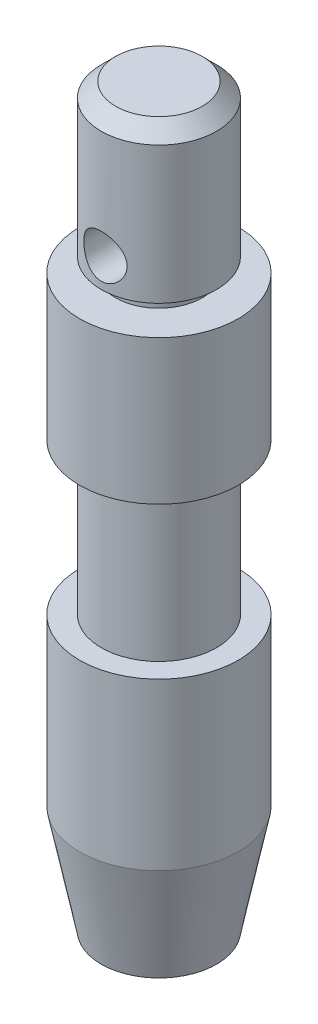
SolidWorks part; units mm, degrees
ref_plane "Plan de face" through (0, 0, 0) normal (0, 0, 1) x (1, 0, 0)
ref_plane "Plan de dessus" through (0, 0, 0) normal (0, 1, 0) x (1, 0, 0)
ref_plane "Plan de droite" through (0, 0, 0) normal (1, 0, 0) x (0, 0, -1)
sketch "Esquisse2" plane through (0, 0, 0) normal (0, 1, 0) x (1, 0, 0)
  circle A0 centre (0, 0) radius 5.5
  dimension "D1" = 11
extrude "Boss.-Extru.2" add sketch "Esquisse2" along normal blind 19 contours A0
chamfer "Chanfrein1" distance 1.5 distance2 7.5 1 edges at (0, 0, 5.5) first distance on face at (0, 0, 5.5)
sketch "Esquisse8" plane through (0, 19, 0) normal (0, 1, 0) x (1, 0, 0)
  circle A0 centre (0, 0) radius 4
  dimension "D1" = 8
extrude "Boss.-Extru.3" add sketch "Esquisse8" along normal blind 10.5
sketch "Esquisse9" plane through (0, 29.5, 0) normal (0, 1, 0) x (1, 0, 0)
  circle A0 centre (0, 0) radius 5.5
  dimension "D1" = 11
extrude "Boss.-Extru.4" add sketch "Esquisse9" along normal blind 10
sketch "Esquisse10" plane through (0, 39.5, 0) normal (0, 1, 0) x (1, 0, 0)
  circle A0 centre (0, 0) radius 3
  dimension "D1" = 6
extrude "Boss.-Extru.5" add sketch "Esquisse10" along normal blind 1
sketch "Esquisse12" plane through (0, 40.5, 0) normal (0, 1, 0) x (1, 0, 0)
  circle A0 centre (0, 0) radius 4
  dimension "D1" = 8
extrude "Boss.-Extru.6" add sketch "Esquisse12" along normal blind 10.5
chamfer "Chanfrein2" distance 1 distance2 1 1 edges at (0, 51, 4)
sketch "Esquisse15" plane through (0, 0, 0) normal (0, 0, 1) x (1, 0, 0)
  line L0 (0, 40.5) -> (0, 42.5)
  line L1 (-3, 40.5) -> (3, 40.5) construction
  circle A0 centre (0, 42.5) radius 1.5
  dimension "D2" = 3
  dimension "D1" = 2
extrude "Enlèv. mat.-Extru.1" cut sketch "Esquisse15" against normal through all both and the other way through all contours A0
